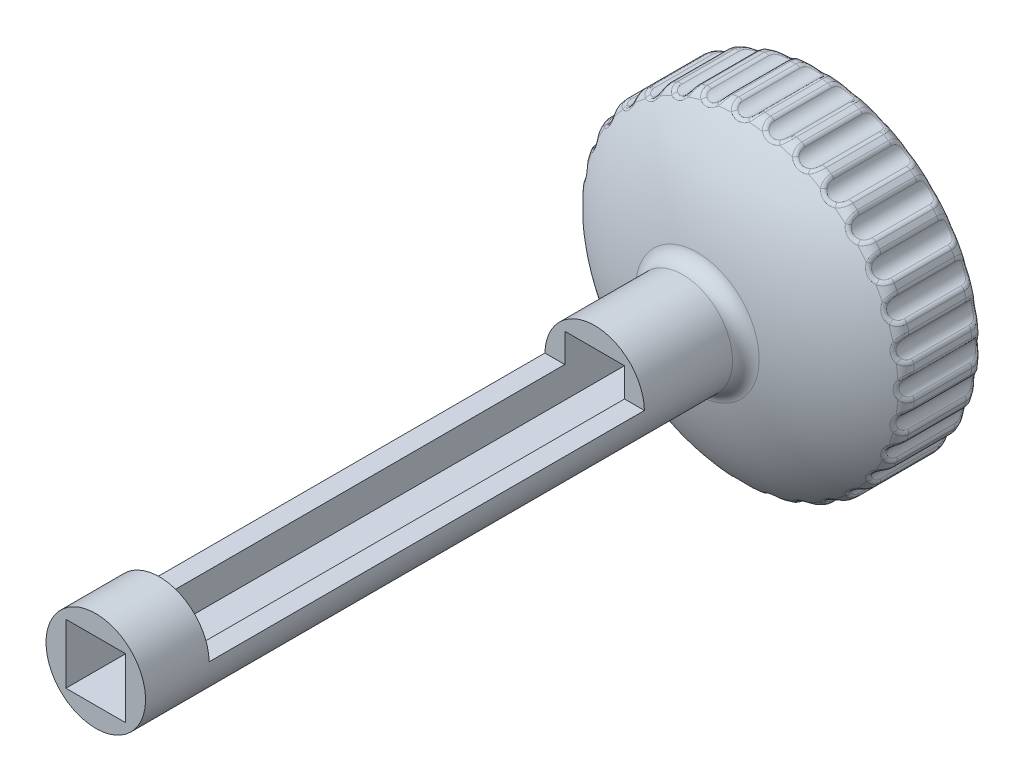
SolidWorks part; units mm, degrees
ref_plane "Front Plane" through (0, 0, 0) normal (0, 0, 1) x (1, 0, 0)
ref_plane "Top Plane" through (0, 0, 0) normal (0, 1, 0) x (1, 0, 0)
ref_plane "Right Plane" through (0, 0, 0) normal (1, 0, 0) x (0, 0, -1)
sketch "Sketch1" plane through (0, 0, 0) normal (1, 0, 0) x (0, 0, -1)
  line L2 (2.1108, -1.5209) -> (-0.9233, -1.5209)
  line L3 (0.1542, 1.7547) -> (1.6542, 1.7547)
  line L4 (2.1108, -1.5209) -> (2.1108, 0.4791)
  line L5 (1.6542, 1.7547) -> (2.1108, 0.4791)
  spline S0 degree 3 poles (-0.9233, -1.5209) (-0.9233, -0.2029) (-0.5276, 1.0077) (0.1542, 1.7547) knots 0 0 0 0 0.621386 0.621386 0.621386 0.621386
  dimension "D1" = 1.5
  dimension "D2" = 2
revolve "Revolve1" add sketch "Sketch1" angle 360 about L2
sketch "Sketch2" plane through (0, 0, -2.1108) normal (0, 0, -1) x (-1, 0, 0)
  circle A0 centre (0, -1.5209) radius 1
  dimension "D1" = 2
extrude "Boss-Extrude1" add sketch "Sketch2" against normal blind 15
fillet "Fillet1" radius 0.3 1 edges at (-1, -1.5209, 0.845)
fillet "Fillet2" radius 0.3 1 edges at (-3.2756, -1.5209, -0.1542)
fillet "Fillet3" radius 0.3 1 edges at (-3.2756, -1.5209, -1.6542)
fillet "Fillet4" radius 0.3 1 edges at (-2, -1.5209, -2.1108)
sketch "Sketch3" plane through (0, 0, -2.1108) normal (0, 0, -1) x (-1, 0, 0)
  line L0 (0, -1.5209) -> (0, 2.7826) construction
  circle A0 centre (0, 1.882) radius 0.25
  circle A1 centre (0.6639, 1.8166) radius 0.25
  circle A2 centre (1.3023, 1.623) radius 0.25
  circle A3 centre (1.8906, 1.3085) radius 0.25
  circle A4 centre (2.4062, 0.8853) radius 0.25
  circle A5 centre (2.8294, 0.3696) radius 0.25
  circle A6 centre (3.1439, -0.2187) radius 0.25
  circle A7 centre (3.3376, -0.8571) radius 0.25
  circle A8 centre (3.4029, -1.5209) radius 0.25
  circle A9 centre (3.3376, -2.1848) radius 0.25
  circle A10 centre (3.1439, -2.8232) radius 0.25
  circle A11 centre (2.8294, -3.4115) radius 0.25
  circle A12 centre (2.4062, -3.9272) radius 0.25
  circle A13 centre (1.8906, -4.3504) radius 0.25
  circle A14 centre (1.3023, -4.6649) radius 0.25
  circle A15 centre (0.6639, -4.8585) radius 0.25
  circle A16 centre (0, -4.9239) radius 0.25
  circle A17 centre (-0.6639, -4.8585) radius 0.25
  circle A18 centre (-1.3023, -4.6649) radius 0.25
  circle A19 centre (-1.8906, -4.3504) radius 0.25
  circle A20 centre (-2.4062, -3.9272) radius 0.25
  circle A21 centre (-2.8294, -3.4115) radius 0.25
  circle A22 centre (-3.1439, -2.8232) radius 0.25
  circle A23 centre (-3.3376, -2.1848) radius 0.25
  circle A24 centre (-3.4029, -1.5209) radius 0.25
  circle A25 centre (-3.3376, -0.8571) radius 0.25
  circle A26 centre (-3.1439, -0.2187) radius 0.25
  circle A27 centre (-2.8294, 0.3696) radius 0.25
  circle A28 centre (-2.4062, 0.8853) radius 0.25
  circle A29 centre (-1.8906, 1.3085) radius 0.25
  circle A30 centre (-1.3023, 1.623) radius 0.25
  circle A31 centre (-0.6639, 1.8166) radius 0.25
  point P46 (0, -1.5209)
  dimension "D2" = 0.5
  dimension "D1" = 32
extrude "Cut-Extrude1" cut sketch "Sketch3" against normal blind 10
fillet "Fillet5" radius 0.1 192 edges at (2.1622, -3.9815, -0.8669) (2.4606, -3.6832, -0.8669) (2.1563, -3.9217, -0.127) (2.4162, -3.6774, -0.1464) (2.2422, -3.7385, -0.0487) (1.6406, -4.3561, -0.8669) (1.9915, -4.1217, -0.8669) (1.6465, -4.2962, -0.127) (1.9394, -4.1052, -0.1334) (1.7665, -4.1333, -0.0487) (1.056, -4.6217, -0.8669) (1.4458, -4.4602, -0.8669) (1.0735, -4.5641, -0.127) (1.3979, -4.4339, -0.1334) (1.2229, -4.4278, -0.0487) (2.2206, -3.7598, -1.6847) (1.7411, -4.15, -1.6847) (1.1948, -4.4391, -1.6847) (3.2688, -1.7319, -0.8669) (3.2688, -1.31, -0.8669) (3.2223, -1.6938, -0.127) (3.2262, -1.3442, -0.1334) (3.1536, -1.5035, -0.0487) (3.2472, -1.0902, -0.8669) (3.1649, -0.6763, -0.8669) (3.1941, -1.0618, -0.127) (3.1297, -0.7182, -0.1334) (3.0896, -0.8886, -0.0487) (3.1007, -0.4649, -0.8669) (2.9393, -0.0751, -0.8669) (3.0431, -0.4475, -0.127) (2.9129, -0.123, -0.1334) (2.9068, -0.298, -0.0487) (2.8351, 0.1197, -0.8669) (2.6007, 0.4705, -0.8669) (2.7753, 0.1256, -0.127) (2.5843, 0.4184, -0.1334) (2.6124, 0.2456, -0.0487) (2.4606, 0.6413, -0.8669) (2.1622, 0.9396, -0.8669) (2.4007, 0.6354, -0.127) (2.1566, 0.8983, -0.1508) (2.2176, 0.7213, -0.0487) (1.9915, 1.0798, -0.8669) (1.6406, 1.3142, -0.8669) (1.9339, 1.0623, -0.127) (1.6454, 1.2597, -0.1334) (1.7375, 1.1108, -0.0487) (1.4458, 1.4183, -0.8669) (1.056, 1.5798, -0.8669) (1.3928, 1.3899, -0.127) (1.0713, 1.5273, -0.1334) (1.1907, 1.3992, -0.0487) (0.8446, 1.6439, -0.8669) (0.4308, 1.7262, -0.8669) (0.7981, 1.6057, -0.127) (0.456, 1.6777, -0.1334) (0.5981, 1.5754, -0.0487) (0.211, 1.7479, -0.8669) (-0.211, 1.7479, -0.8669) (0.1728, 1.7013, -0.127) (-0.1768, 1.7052, -0.1334) (-0.0174, 1.6326, -0.0487) (-0.4308, 1.7262, -0.8669) (-0.8446, 1.6439, -0.8669) (-0.4591, 1.6731, -0.127) (-0.8028, 1.6088, -0.1334) (-0.6323, 1.5686, -0.0487) (-1.056, 1.5798, -0.8669) (-1.4458, 1.4183, -0.8669) (-1.0735, 1.5222, -0.127) (-1.3979, 1.392, -0.1334) (-1.2229, 1.3859, -0.0487) (-1.6406, 1.3142, -0.8669) (-1.9915, 1.0798, -0.8669) (-1.6465, 1.2543, -0.127) (-1.9394, 1.0633, -0.1334) (-1.7665, 1.0915, -0.0487) (-2.1622, 0.9396, -0.8669) (-2.4606, 0.6413, -0.8669) (-2.1563, 0.8798, -0.127) (-2.4193, 0.6356, -0.1508) (-2.2422, 0.6966, -0.0487) (-2.6007, 0.4705, -0.8669) (-2.8351, 0.1197, -0.8669) (-2.5832, 0.413, -0.127) (-2.7807, 0.1244, -0.1334) (-2.6318, 0.2166, -0.0487) (-2.9393, -0.0751, -0.8669) (-3.1007, -0.4649, -0.8669) (-2.9109, -0.1282, -0.127) (-3.0483, -0.4497, -0.1334) (-2.9202, -0.3302, -0.0487) (-3.1649, -0.6763, -0.8669) (-3.2472, -1.0902, -0.8669) (-3.1267, -0.7228, -0.127) (-3.1987, -1.0649, -0.1334) (-3.0964, -0.9228, -0.0487) (-3.2688, -1.31, -0.8669) (-3.2688, -1.7319, -0.8669) (-3.2223, -1.3481, -0.127) (-3.2262, -1.6977, -0.1334) (-3.1536, -1.5384, -0.0487) (-3.2472, -1.9517, -0.8669) (-3.1649, -2.3656, -0.8669) (-3.1941, -1.9801, -0.127) (-3.1297, -2.3237, -0.1334) (-3.0896, -2.1533, -0.0487) (-3.1007, -2.577, -0.8669) (-2.9393, -2.9668, -0.8669) (-3.0431, -2.5944, -0.127) (-2.9129, -2.9189, -0.1334) (-2.9068, -2.7439, -0.0487) (-2.8351, -3.1616, -0.8669) (-2.6007, -3.5124, -0.8669) (-2.7753, -3.1675, -0.127) (-2.5843, -3.4603, -0.1334) (-2.6124, -3.2875, -0.0487) (-2.4606, -3.6832, -0.8669) (-2.1622, -3.9815, -0.8669) (-2.4007, -3.6773, -0.127) (-2.1566, -3.9402, -0.1508) (-2.2176, -3.7632, -0.0487) (-1.9915, -4.1217, -0.8669) (-1.6406, -4.3561, -0.8669) (-1.9339, -4.1042, -0.127) (-1.6454, -4.3016, -0.1334) (-1.7375, -4.1527, -0.0487) (-1.4458, -4.4602, -0.8669) (-1.056, -4.6217, -0.8669) (-1.3928, -4.4318, -0.127) (-1.0713, -4.5692, -0.1334) (-1.1907, -4.4411, -0.0487) (-0.8446, -4.6858, -0.8669) (-0.4308, -4.7681, -0.8669) (-0.7981, -4.6476, -0.127) (-0.456, -4.7196, -0.1334) (-0.5981, -4.6173, -0.0487) (-0.211, -4.7898, -0.8669) (0.211, -4.7898, -0.8669) (-0.1728, -4.7432, -0.127) (0.1768, -4.7471, -0.1334) (0.0174, -4.6745, -0.0487) (0.4308, -4.7681, -0.8669) (0.8446, -4.6858, -0.8669) (0.4591, -4.715, -0.127) (0.8028, -4.6506, -0.1334) (0.6323, -4.6105, -0.0487) (3.1649, -2.3656, -0.8669) (3.2472, -1.9517, -0.8669) (3.1267, -2.3191, -0.127) (3.1987, -1.977, -0.1334) (3.0964, -2.1191, -0.0487) (2.9393, -2.9668, -0.8669) (3.1007, -2.577, -0.8669) (2.9109, -2.9137, -0.127) (3.0483, -2.5922, -0.1334) (2.9202, -2.7117, -0.0487) (2.6007, -3.5124, -0.8669) (2.8351, -3.1616, -0.8669) (2.5832, -3.4549, -0.127) (2.7807, -3.1663, -0.1334) (2.6318, -3.2585, -0.0487) (3.1533, -1.5339, -1.6847) (3.0952, -0.9185, -1.6847) (2.9182, -0.3262, -1.6847) (2.629, 0.2202, -1.6847) (2.2388, 0.6996, -1.6847) (1.7626, 1.0937, -1.6847) (1.2187, 1.3874, -1.6847) (0.6279, 1.5692, -1.6847) (0.0129, 1.6323, -1.6847) (-0.6025, 1.5743, -1.6847) (-1.1948, 1.3973, -1.6847) (-1.7411, 1.1081, -1.6847) (-2.2206, 0.7179, -1.6847) (-2.6147, 0.2417, -1.6847) (-2.9083, -0.3023, -1.6847) (-3.0902, -0.8931, -1.6847) (-3.1533, -1.508, -1.6847) (-3.0952, -2.1234, -1.6847) (-2.9182, -2.7157, -1.6847) (-2.629, -3.2621, -1.6847) (-2.2388, -3.7415, -1.6847) (-1.7626, -4.1356, -1.6847) (-1.2187, -4.4292, -1.6847) (-0.6279, -4.6111, -1.6847) (-0.0129, -4.6742, -1.6847) (0.6025, -4.6162, -1.6847) (3.0902, -2.1488, -1.6847) (2.9083, -2.7396, -1.6847) (2.6147, -3.2836, -1.6847)
sketch "Sketch4" plane through (0, 0, -2.1108) normal (0, 0, -1) x (-1, 0, 0)
  line L1 (-0.6, -2.1209) -> (0.6, -2.1209)
  line L2 (-0.6, -2.1209) -> (-0.6, -0.9209)
  line L3 (-0.6, -0.9209) -> (0.6, -0.9209)
  line L4 (0.6, -2.1209) -> (0.6, -0.9209)
  line L5 (-0.6, -2.1209) -> (0.6, -0.9209) construction
  line L6 (-0.6, -0.9209) -> (0.6, -2.1209) construction
  point P0 (0, -1.5209)
  point P1 (0, -1.5209)
  dimension "D1" = 1.2
  dimension "D2" = 1.2
extrude "Cut-Extrude4" cut sketch "Sketch4" against normal through all
sketch "Sketch5" plane through (0, 0, 0) normal (0, 1, 0) x (1, 0, 0)
  line L0 (-2.2804, -2.8653) -> (2.4133, -2.8653)
  line L1 (2.4133, -2.8653) -> (2.4133, -11.6106)
  line L2 (2.4133, -11.6106) -> (-2.2804, -11.6106)
  line L3 (-2.2804, -11.6106) -> (-2.2804, -2.8653)
extrude "Cut-Extrude5" cut sketch "Sketch5" against normal blind 1.5
sketch "Sketch6" plane through (0, 0, -2.1108) normal (0, 0, -1) x (-1, 0, 0)
  circle A0 centre (0, -1.5209) radius 2
  dimension "D1" = 4
extrude "Cut-Extrude6" cut sketch "Sketch6" against normal blind 0.2
fillet "Fillet6" radius 0.05 1 edges at (2, -1.5209, -2.1062)
